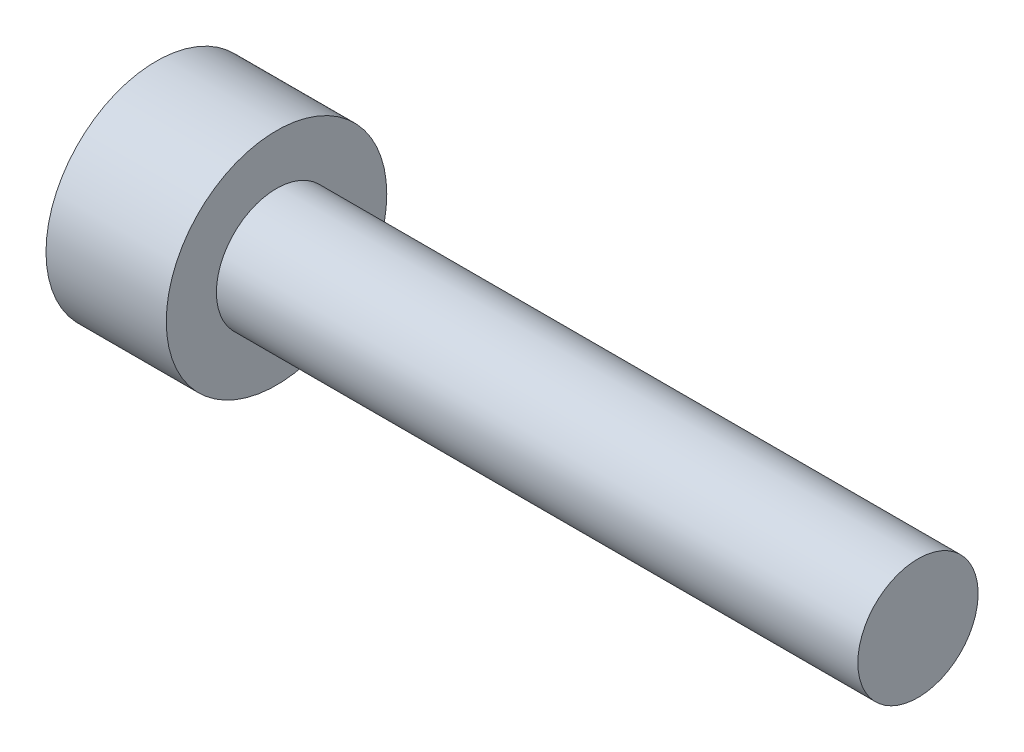
SolidWorks part; units mm, degrees
ref_plane "Front Plane" through (0, 0, 0) normal (0, 0, 1) x (1, 0, 0)
ref_plane "Top Plane" through (0, 0, 0) normal (0, 1, 0) x (1, 0, 0)
ref_plane "Right Plane" through (0, 0, 0) normal (1, 0, 0) x (0, 0, -1)
sketch "Screw Sketch" plane through (0, 0, 0) normal (0, 0, 1) x (1, 0, 0)
  line L0 (-1000, 0) -> (1000, 0) construction
  line L1 (-3, 0) -> (-3, 2.75)
  line L2 (-3, 2.75) -> (0, 2.75)
  line L3 (0, 2.75) -> (0, 1.5)
  line L4 (0, 1.5) -> (16, 1.5)
  line L5 (16, 1.5) -> (16, 0)
  line L6 (16, 0) -> (-3, 0)
revolve "Screw" add sketch "Screw Sketch" angle 360 about L0
ref_axis "Engine Axis" through (16.95, 0, 0) along (-1, 0, 0)
ref_plane "Head Top" through (-3, 0, 0) normal (1, 0, 0) x (0, 0, -1)
sketch "Socket Sketch" plane through (-3, 0, 0) normal (1, 0, 0) x (0, 0, -1)
  line L0 (1.4434, 0) -> (0.7217, 1.25)
  line L1 (0.7217, 1.25) -> (-0.7217, 1.25)
  line L2 (-0.7217, 1.25) -> (-1.4434, 0)
  line L3 (-1.4434, 0) -> (-0.7217, -1.25)
  line L4 (-0.7217, -1.25) -> (0.7217, -1.25)
  line L5 (0.7217, -1.25) -> (1.4434, 0)
extrude "Socket" cut sketch "Socket Sketch" along normal blind 1.5
